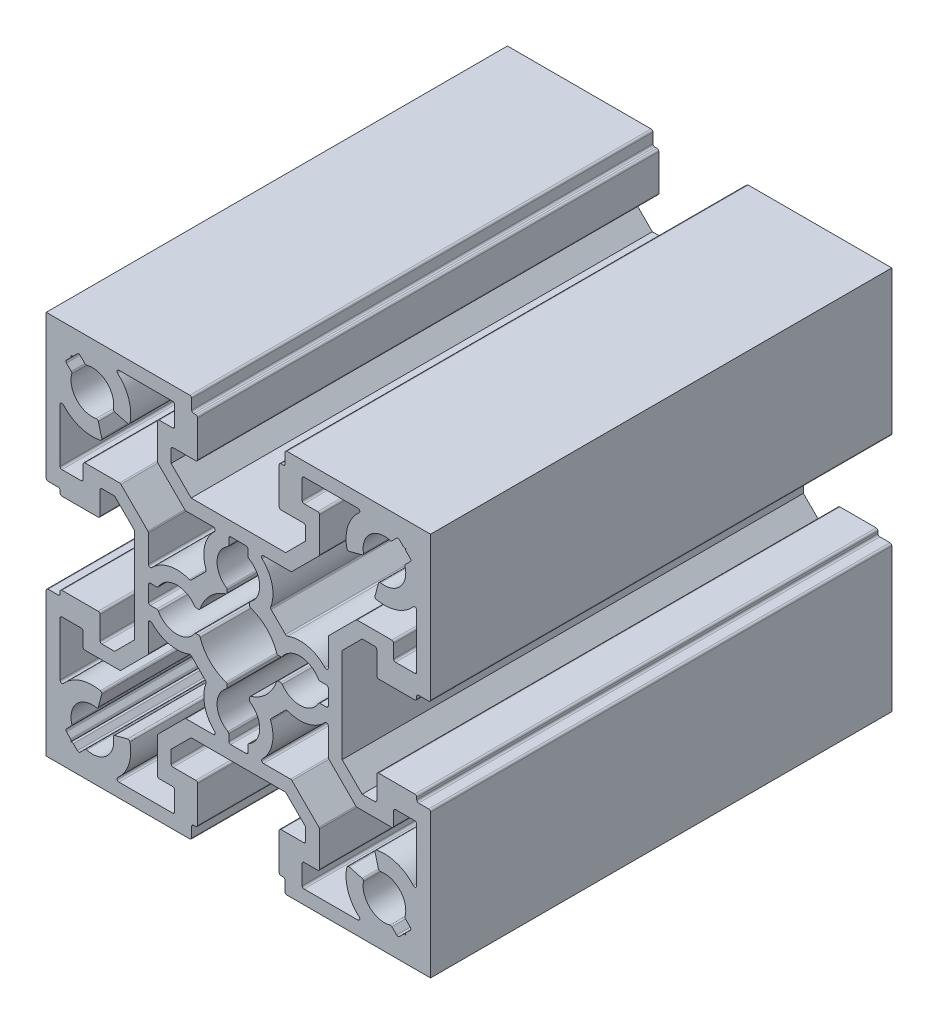
SolidWorks part; units mm, degrees
material "6061 Alaşım"
ref_plane "Ön Düzlem" through (0, 0, 0) normal (0, 0, 1) x (1, 0, 0)
ref_plane "Üst Düzlem" through (0, 0, 0) normal (0, 1, 0) x (1, 0, 0)
ref_plane "Sağ Düzlem" through (0, 0, 0) normal (1, 0, 0) x (0, 0, -1)
sketch "Çizim1" plane through (0, 0, 0) normal (0, 0, 1) x (1, 0, 0)
  line L1 (25, -25) -> (-25, -25) construction
  line L2 (25, -25) -> (25, 25) construction
  line L3 (25, 25) -> (-25, 25) construction
  line L4 (-25, -25) -> (-25, 25) construction
  line L5 (25, -25) -> (-25, 25) construction
  line L6 (25, 25) -> (-25, -25) construction
  point P0 (0, 0)
  dimension "D1" = 50
  dimension "D2" = 50
sketch "Çizim3" plane through (0, 0, 0) normal (0, 0, 1) x (1, 0, 0)
  line L0 (6.075, -24.75) -> (6.075, -23.45)
  line L1 (25, -25) -> (-25, -25) construction
  line L2 (5.825, -23.2) -> (5.55, -23.2)
  line L3 (5.3, -22.95) -> (5.3, -18.25)
  line L4 (5.55, -18) -> (8.5, -18)
  line L5 (8.75, -17.75) -> (8.75, -16.1)
  line L6 (8.75, -16.1) -> (6.15, -13.5)
  line L7 (6.15, -13.5) -> (0, -13.5)
  line L8 (0, -25) -> (0, 25) construction
  line L9 (25, 25) -> (-25, 25) construction
  line L10 (25, -25) -> (-25, 25) construction
  line L11 (6.325, -25) -> (25, -25)
  line L12 (3.265, -11.7) -> (6.792, -11.7)
  line L13 (6.9688, -11.7732) -> (10.4768, -15.2812)
  line L14 (10.55, -15.458) -> (10.55, -19.95)
  line L15 (10.3, -20.2) -> (8.55, -20.2)
  line L16 (8.3, -20.45) -> (8.3, -22.95)
  line L17 (8.55, -23.2) -> (15.5417, -23.2)
  line L18 (25, -25) -> (25, 25) construction
  line L19 (17.7059, -14.1704) -> (19, -19) construction
  line L20 (19, -19) -> (14.1704, -17.7059) construction
  line L21 (25, -25) -> (19, -19) construction
  line L22 (20.9445, -22.3588) -> (21.4749, -21.8284)
  line L23 (19.9736, -21.7414) -> (20.591, -22.3588)
  line L24 (20.7678, -22.5355) -> (22.5355, -20.7678) construction
  line L25 (22.5355, -20.7678) -> (21.6358, -19.868) construction
  line L26 (21.8284, -21.8284) -> (25, -25)
  line L27 (16.0881, -18.2198) -> (14.4182, -17.7723)
  line L28 (0, -11.7) -> (1, -11.7)
  line L29 (1.25, -11.45) -> (1.25, -10.6269)
  line L30 (0, -11.7) -> (0, -13.5)
  line L31 (6.1324, -4.2621) -> (4.2621, -6.1324)
  line L32 (5.1972, -5.1972) -> (3.6946, -3.6946)
  line L33 (1.45, -5.2044) -> (1.45, -5.4979)
  line L34 (18.2198, -16.0881) -> (17.7723, -14.4182)
  line L35 (21.7414, -19.9736) -> (22.3588, -20.591)
  line L36 (22.3588, -20.9445) -> (21.8284, -21.4749)
  line L37 (25, -6.325) -> (25, -25)
  line L38 (24.75, -6.075) -> (23.45, -6.075)
  line L39 (23.2, -5.825) -> (23.2, -5.55)
  line L40 (22.95, -5.3) -> (18.25, -5.3)
  line L41 (18, -5.55) -> (18, -8.5)
  line L42 (17.75, -8.75) -> (16.1, -8.75)
  line L43 (16.1, -8.75) -> (13.5, -6.15)
  line L44 (13.5, -6.15) -> (13.5, 0)
  line L45 (11.7, 0) -> (13.5, 0)
  line L46 (11.7, 0) -> (11.7, -1)
  line L47 (11.45, -1.25) -> (10.6269, -1.25)
  line L48 (5.2044, -1.45) -> (5.4979, -1.45)
  line L49 (11.7, -3.265) -> (11.7, -6.792)
  line L50 (11.7732, -6.9688) -> (15.2812, -10.4768)
  line L51 (15.458, -10.55) -> (19.95, -10.55)
  line L52 (20.2, -10.3) -> (20.2, -8.55)
  line L53 (20.45, -8.3) -> (22.95, -8.3)
  line L54 (23.2, -8.55) -> (23.2, -15.5417)
  line L55 (-20.9445, -22.3588) -> (-21.4749, -21.8284)
  line L56 (-19.9736, -21.7414) -> (-20.591, -22.3588)
  line L57 (-16.0881, -18.2198) -> (-14.4182, -17.7723)
  line L58 (-8.55, -23.2) -> (-15.5417, -23.2)
  line L59 (-8.3, -20.45) -> (-8.3, -22.95)
  line L60 (-10.3, -20.2) -> (-8.55, -20.2)
  line L61 (-10.55, -15.458) -> (-10.55, -19.95)
  line L62 (-6.9688, -11.7732) -> (-10.4768, -15.2812)
  line L63 (-3.265, -11.7) -> (-6.792, -11.7)
  line L64 (-4.2621, -6.1324) -> (-6.1324, -4.2621)
  line L65 (-11.7, -3.265) -> (-11.7, -6.792)
  line L66 (-11.7732, -6.9688) -> (-15.2812, -10.4768)
  line L67 (-15.458, -10.55) -> (-19.95, -10.55)
  line L68 (-20.2, -10.3) -> (-20.2, -8.55)
  line L69 (-20.45, -8.3) -> (-22.95, -8.3)
  line L70 (-23.2, -8.55) -> (-23.2, -15.5417)
  line L71 (-18.2198, -16.0881) -> (-17.7723, -14.4182)
  line L72 (-21.7414, -19.9736) -> (-22.3588, -20.591)
  line L73 (-22.3588, -20.9445) -> (-21.8284, -21.4749)
  line L74 (-25, -6.325) -> (-25, -25)
  line L75 (-24.75, -6.075) -> (-23.45, -6.075)
  line L76 (-23.2, -5.825) -> (-23.2, -5.55)
  line L77 (-22.95, -5.3) -> (-18.25, -5.3)
  line L78 (-18, -5.55) -> (-18, -8.5)
  line L79 (-17.75, -8.75) -> (-16.1, -8.75)
  line L80 (-16.1, -8.75) -> (-13.5, -6.15)
  line L81 (-13.5, -6.15) -> (-13.5, 0)
  line L82 (-11.7, 0) -> (-13.5, 0) construction
  line L83 (-11.7, 0) -> (-11.7, -1)
  line L84 (-11.45, -1.25) -> (-10.6269, -1.25)
  line L85 (-5.2044, -1.45) -> (-5.4979, -1.45)
  line L86 (-1.45, -5.2044) -> (-1.45, -5.4979)
  line L87 (-1.25, -11.45) -> (-1.25, -10.6269)
  line L88 (0, -11.7) -> (-1, -11.7)
  line L89 (0, -11.7) -> (0, -13.5)
  line L90 (-6.15, -13.5) -> (0, -13.5)
  line L91 (-8.75, -16.1) -> (-6.15, -13.5)
  line L92 (-8.75, -17.75) -> (-8.75, -16.1)
  line L93 (-5.55, -18) -> (-8.5, -18)
  line L94 (-5.3, -22.95) -> (-5.3, -18.25)
  line L95 (-5.825, -23.2) -> (-5.55, -23.2)
  line L96 (-6.075, -24.75) -> (-6.075, -23.45)
  line L97 (-6.325, -25) -> (-25, -25)
  line L98 (-22.3588, 20.9445) -> (-21.8284, 21.4749)
  line L99 (-21.7414, 19.9736) -> (-22.3588, 20.591)
  line L100 (-18.2198, 16.0881) -> (-17.7723, 14.4182)
  line L101 (-23.2, 8.55) -> (-23.2, 15.5417)
  line L102 (-20.45, 8.3) -> (-22.95, 8.3)
  line L103 (-20.2, 10.3) -> (-20.2, 8.55)
  line L104 (-15.458, 10.55) -> (-19.95, 10.55)
  line L105 (-11.7732, 6.9688) -> (-15.2812, 10.4768)
  line L106 (-11.7, 3.265) -> (-11.7, 6.792)
  line L107 (-6.1324, 4.2621) -> (-4.2621, 6.1324)
  line L108 (-3.265, 11.7) -> (-6.792, 11.7)
  line L109 (-6.9688, 11.7732) -> (-10.4768, 15.2812)
  line L110 (-10.55, 15.458) -> (-10.55, 19.95)
  line L111 (-10.3, 20.2) -> (-8.55, 20.2)
  line L112 (-8.3, 20.45) -> (-8.3, 22.95)
  line L113 (-8.55, 23.2) -> (-15.5417, 23.2)
  line L114 (-16.0881, 18.2198) -> (-14.4182, 17.7723)
  line L115 (-19.9736, 21.7414) -> (-20.591, 22.3588)
  line L116 (-20.9445, 22.3588) -> (-21.4749, 21.8284)
  line L117 (-6.325, 25) -> (-25, 25)
  line L118 (-6.075, 24.75) -> (-6.075, 23.45)
  line L119 (-5.825, 23.2) -> (-5.55, 23.2)
  line L120 (-5.3, 22.95) -> (-5.3, 18.25)
  line L121 (-5.55, 18) -> (-8.5, 18)
  line L122 (-8.75, 17.75) -> (-8.75, 16.1)
  line L123 (-8.75, 16.1) -> (-6.15, 13.5)
  line L124 (-6.15, 13.5) -> (0, 13.5)
  line L125 (0, 11.7) -> (0, 13.5)
  line L126 (0, 11.7) -> (-1, 11.7)
  line L127 (-1.25, 11.45) -> (-1.25, 10.6269)
  line L128 (-1.45, 5.2044) -> (-1.45, 5.4979)
  line L129 (-5.2044, 1.45) -> (-5.4979, 1.45)
  line L130 (-11.45, 1.25) -> (-10.6269, 1.25)
  line L131 (-11.7, 0) -> (-11.7, 1)
  line L132 (-11.7, 0) -> (-13.5, 0)
  line L133 (-13.5, 6.15) -> (-13.5, 0)
  line L134 (-16.1, 8.75) -> (-13.5, 6.15)
  line L135 (-17.75, 8.75) -> (-16.1, 8.75)
  line L136 (-18, 5.55) -> (-18, 8.5)
  line L137 (-22.95, 5.3) -> (-18.25, 5.3)
  line L138 (-23.2, 5.825) -> (-23.2, 5.55)
  line L139 (-24.75, 6.075) -> (-23.45, 6.075)
  line L140 (-25, 6.325) -> (-25, 25)
  line L141 (20.9445, 22.3588) -> (21.4749, 21.8284)
  line L142 (19.9736, 21.7414) -> (20.591, 22.3588)
  line L143 (16.0881, 18.2198) -> (14.4182, 17.7723)
  line L144 (8.55, 23.2) -> (15.5417, 23.2)
  line L145 (8.3, 20.45) -> (8.3, 22.95)
  line L146 (10.3, 20.2) -> (8.55, 20.2)
  line L147 (10.55, 15.458) -> (10.55, 19.95)
  line L148 (6.9688, 11.7732) -> (10.4768, 15.2812)
  line L149 (3.265, 11.7) -> (6.792, 11.7)
  line L150 (4.2621, 6.1324) -> (6.1324, 4.2621)
  line L151 (11.7, 3.265) -> (11.7, 6.792)
  line L152 (11.7732, 6.9688) -> (15.2812, 10.4768)
  line L153 (15.458, 10.55) -> (19.95, 10.55)
  line L154 (20.2, 10.3) -> (20.2, 8.55)
  line L155 (20.45, 8.3) -> (22.95, 8.3)
  line L156 (23.2, 8.55) -> (23.2, 15.5417)
  line L157 (18.2198, 16.0881) -> (17.7723, 14.4182)
  line L158 (21.7414, 19.9736) -> (22.3588, 20.591)
  line L159 (22.3588, 20.9445) -> (21.8284, 21.4749)
  line L160 (25, 6.325) -> (25, 25)
  line L161 (24.75, 6.075) -> (23.45, 6.075)
  line L162 (23.2, 5.825) -> (23.2, 5.55)
  line L163 (22.95, 5.3) -> (18.25, 5.3)
  line L164 (18, 5.55) -> (18, 8.5)
  line L165 (17.75, 8.75) -> (16.1, 8.75)
  line L166 (16.1, 8.75) -> (13.5, 6.15)
  line L167 (13.5, 6.15) -> (13.5, 0)
  line L168 (11.7, 0) -> (13.5, 0)
  line L169 (11.7, 0) -> (11.7, 1)
  line L170 (11.45, 1.25) -> (10.6269, 1.25)
  line L171 (5.2044, 1.45) -> (5.4979, 1.45)
  line L172 (1.45, 5.2044) -> (1.45, 5.4979)
  line L173 (1.25, 11.45) -> (1.25, 10.6269)
  line L174 (0, 11.7) -> (1, 11.7)
  line L175 (0, 11.7) -> (0, 13.5)
  line L176 (6.15, 13.5) -> (0, 13.5)
  line L177 (8.75, 16.1) -> (6.15, 13.5)
  line L178 (8.75, 17.75) -> (8.75, 16.1)
  line L179 (5.55, 18) -> (8.5, 18)
  line L180 (5.3, 22.95) -> (5.3, 18.25)
  line L181 (5.825, 23.2) -> (5.55, 23.2)
  line L182 (6.075, 24.75) -> (6.075, 23.45)
  line L183 (6.325, 25) -> (25, 25)
  circle A0 centre (19, -19) radius 2.775 construction
  circle A1 centre (0, -8) radius 2.775 construction
  circle A2 centre (19, -19) radius 5 construction
  arc A3 (14.109, -17.9619) -> (15.7064, -22.7619) centre (19, -19) ccw
  arc A4 (16.2694, -18.5058) -> (19.731, -21.677) centre (19, -19) ccw
  circle A5 centre (0, -8) radius 4.5 construction
  arc A6 (3.0931, -11.2684) -> (4.2052, -6.3981) centre (0, -8) ccw
  circle A7 centre (0, 0) radius 5.225 construction
  arc A8 (4.9667, -1.6224) -> (1.6224, -4.9667) centre (0, 0) cw
  arc A9 (1.5595, -5.7047) -> (1.376, -10.4098) centre (0, -8) cw
  arc A10 (14.4182, -17.7723) -> (14.109, -17.9619) centre (14.3535, -18.0138) ccw
  arc A11 (16.2694, -18.5058) -> (16.0881, -18.2198) centre (16.0234, -18.4612) ccw
  arc A12 (21.4749, -21.8284) -> (21.8284, -21.8284) centre (21.6517, -22.0052) cw
  arc A13 (19.9736, -21.7414) -> (19.731, -21.677) centre (19.7968, -21.9182) ccw
  arc A14 (20.591, -22.3588) -> (20.9445, -22.3588) centre (20.7678, -22.182) ccw
  arc A15 (4.2052, -6.3981) -> (4.2621, -6.1324) centre (4.4389, -6.3092) cw
  arc A16 (1.6224, -4.9667) -> (1.45, -5.2044) centre (1.7, -5.2044) ccw
  arc A17 (1.45, -5.4979) -> (1.5595, -5.7047) centre (1.7, -5.4979) ccw
  arc A18 (1.25, -10.6269) -> (1.376, -10.4098) centre (1.5, -10.6269) cw
  arc A19 (1, -11.7) -> (1.25, -11.45) centre (1, -11.45) ccw
  arc A20 (3.265, -11.7) -> (3.0931, -11.2684) centre (3.265, -11.45) cw
  arc A21 (6.792, -11.7) -> (6.9688, -11.7732) centre (6.792, -11.95) cw
  arc A22 (10.4768, -15.2812) -> (10.55, -15.458) centre (10.3, -15.458) cw
  arc A23 (15.5417, -23.2) -> (15.7064, -22.7619) centre (15.5417, -22.95) ccw
  arc A24 (8.3, -22.95) -> (8.55, -23.2) centre (8.55, -22.95) ccw
  arc A25 (8.55, -20.2) -> (8.3, -20.45) centre (8.55, -20.45) ccw
  arc A26 (10.55, -19.95) -> (10.3, -20.2) centre (10.3, -19.95) cw
  arc A27 (6.075, -24.75) -> (6.325, -25) centre (6.325, -24.75) ccw
  arc A28 (6.075, -23.45) -> (5.825, -23.2) centre (5.825, -23.45) ccw
  arc A29 (5.55, -23.2) -> (5.3, -22.95) centre (5.55, -22.95) cw
  arc A30 (5.3, -18.25) -> (5.55, -18) centre (5.55, -18.25) cw
  arc A31 (8.5, -18) -> (8.75, -17.75) centre (8.5, -17.75) ccw
  arc A32 (18.5058, -16.2694) -> (18.2198, -16.0881) centre (18.4612, -16.0234) cw
  arc A33 (18.5058, -16.2694) -> (21.677, -19.731) centre (19, -19) cw
  arc A34 (21.7414, -19.9736) -> (21.677, -19.731) centre (21.9182, -19.7968) cw
  arc A35 (22.3588, -20.591) -> (22.3588, -20.9445) centre (22.182, -20.7678) cw
  arc A36 (21.8284, -21.4749) -> (21.8284, -21.8284) centre (22.0052, -21.6517) ccw
  arc A37 (24.75, -6.075) -> (25, -6.325) centre (24.75, -6.325) cw
  arc A38 (23.45, -6.075) -> (23.2, -5.825) centre (23.45, -5.825) cw
  arc A39 (23.2, -5.55) -> (22.95, -5.3) centre (22.95, -5.55) ccw
  arc A40 (18.25, -5.3) -> (18, -5.55) centre (18.25, -5.55) ccw
  arc A41 (18, -8.5) -> (17.75, -8.75) centre (17.75, -8.5) cw
  arc A42 (11.7, -1) -> (11.45, -1.25) centre (11.45, -1) cw
  arc A43 (10.6269, -1.25) -> (10.4098, -1.376) centre (10.6269, -1.5) ccw
  arc A44 (5.7047, -1.5595) -> (10.4098, -1.376) centre (8, 0) ccw
  arc A45 (5.4979, -1.45) -> (5.7047, -1.5595) centre (5.4979, -1.7) cw
  arc A46 (4.9667, -1.6224) -> (5.2044, -1.45) centre (5.2044, -1.7) cw
  arc A47 (6.3981, -4.2052) -> (6.1324, -4.2621) centre (6.3092, -4.4389) ccw
  arc A48 (11.2684, -3.0931) -> (6.3981, -4.2052) centre (8, 0) cw
  arc A49 (11.7, -3.265) -> (11.2684, -3.0931) centre (11.45, -3.265) ccw
  arc A50 (11.7, -6.792) -> (11.7732, -6.9688) centre (11.95, -6.792) ccw
  arc A51 (15.2812, -10.4768) -> (15.458, -10.55) centre (15.458, -10.3) ccw
  arc A52 (19.95, -10.55) -> (20.2, -10.3) centre (19.95, -10.3) ccw
  arc A53 (20.2, -8.55) -> (20.45, -8.3) centre (20.45, -8.55) cw
  arc A54 (22.95, -8.3) -> (23.2, -8.55) centre (22.95, -8.55) cw
  arc A55 (23.2, -15.5417) -> (22.7619, -15.7064) centre (22.95, -15.5417) cw
  arc A56 (17.9619, -14.109) -> (22.7619, -15.7064) centre (19, -19) cw
  arc A57 (17.7723, -14.4182) -> (17.9619, -14.109) centre (18.0138, -14.3535) cw
  arc A58 (-21.4749, -21.8284) -> (-21.8284, -21.8284) centre (-21.6517, -22.0052) ccw
  arc A59 (-20.591, -22.3588) -> (-20.9445, -22.3588) centre (-20.7678, -22.182) cw
  arc A60 (-19.9736, -21.7414) -> (-19.731, -21.677) centre (-19.7968, -21.9182) cw
  arc A61 (-16.2694, -18.5058) -> (-19.731, -21.677) centre (-19, -19) cw
  arc A62 (-16.2694, -18.5058) -> (-16.0881, -18.2198) centre (-16.0234, -18.4612) cw
  arc A63 (-14.4182, -17.7723) -> (-14.109, -17.9619) centre (-14.3535, -18.0138) cw
  arc A64 (-14.109, -17.9619) -> (-15.7064, -22.7619) centre (-19, -19) cw
  arc A65 (-15.5417, -23.2) -> (-15.7064, -22.7619) centre (-15.5417, -22.95) cw
  arc A66 (-8.3, -22.95) -> (-8.55, -23.2) centre (-8.55, -22.95) cw
  arc A67 (-8.55, -20.2) -> (-8.3, -20.45) centre (-8.55, -20.45) cw
  arc A68 (-10.55, -19.95) -> (-10.3, -20.2) centre (-10.3, -19.95) ccw
  arc A69 (-10.4768, -15.2812) -> (-10.55, -15.458) centre (-10.3, -15.458) ccw
  arc A70 (-6.792, -11.7) -> (-6.9688, -11.7732) centre (-6.792, -11.95) ccw
  arc A71 (-3.265, -11.7) -> (-3.0931, -11.2684) centre (-3.265, -11.45) ccw
  arc A72 (-3.0931, -11.2684) -> (-4.2052, -6.3981) centre (0, -8) cw
  arc A73 (-4.2052, -6.3981) -> (-4.2621, -6.1324) centre (-4.4389, -6.3092) ccw
  arc A74 (-6.3981, -4.2052) -> (-6.1324, -4.2621) centre (-6.3092, -4.4389) cw
  arc A75 (-11.2684, -3.0931) -> (-6.3981, -4.2052) centre (-8, 0) ccw
  arc A76 (-11.7, -3.265) -> (-11.2684, -3.0931) centre (-11.45, -3.265) cw
  arc A77 (-11.7, -6.792) -> (-11.7732, -6.9688) centre (-11.95, -6.792) cw
  arc A78 (-15.2812, -10.4768) -> (-15.458, -10.55) centre (-15.458, -10.3) cw
  arc A79 (-19.95, -10.55) -> (-20.2, -10.3) centre (-19.95, -10.3) cw
  arc A80 (-20.2, -8.55) -> (-20.45, -8.3) centre (-20.45, -8.55) ccw
  arc A81 (-22.95, -8.3) -> (-23.2, -8.55) centre (-22.95, -8.55) ccw
  arc A82 (-23.2, -15.5417) -> (-22.7619, -15.7064) centre (-22.95, -15.5417) ccw
  arc A83 (-17.9619, -14.109) -> (-22.7619, -15.7064) centre (-19, -19) ccw
  arc A84 (-17.7723, -14.4182) -> (-17.9619, -14.109) centre (-18.0138, -14.3535) ccw
  arc A85 (-18.5058, -16.2694) -> (-18.2198, -16.0881) centre (-18.4612, -16.0234) ccw
  arc A86 (-18.5058, -16.2694) -> (-21.677, -19.731) centre (-19, -19) ccw
  arc A87 (-21.7414, -19.9736) -> (-21.677, -19.731) centre (-21.9182, -19.7968) ccw
  arc A88 (-22.3588, -20.591) -> (-22.3588, -20.9445) centre (-22.182, -20.7678) ccw
  arc A89 (-21.8284, -21.4749) -> (-21.8284, -21.8284) centre (-22.0052, -21.6517) cw
  arc A90 (-24.75, -6.075) -> (-25, -6.325) centre (-24.75, -6.325) ccw
  arc A91 (-23.45, -6.075) -> (-23.2, -5.825) centre (-23.45, -5.825) ccw
  arc A92 (-23.2, -5.55) -> (-22.95, -5.3) centre (-22.95, -5.55) cw
  arc A93 (-18.25, -5.3) -> (-18, -5.55) centre (-18.25, -5.55) cw
  arc A94 (-18, -8.5) -> (-17.75, -8.75) centre (-17.75, -8.5) ccw
  arc A95 (-11.7, -1) -> (-11.45, -1.25) centre (-11.45, -1) ccw
  arc A96 (-10.6269, -1.25) -> (-10.4098, -1.376) centre (-10.6269, -1.5) cw
  arc A97 (-5.7047, -1.5595) -> (-10.4098, -1.376) centre (-8, 0) cw
  arc A98 (-5.4979, -1.45) -> (-5.7047, -1.5595) centre (-5.4979, -1.7) ccw
  arc A99 (-4.9667, -1.6224) -> (-5.2044, -1.45) centre (-5.2044, -1.7) ccw
  arc A100 (-1.6224, -4.9667) -> (-4.9667, -1.6224) centre (0, 0) cw
  arc A101 (-1.6224, -4.9667) -> (-1.45, -5.2044) centre (-1.7, -5.2044) cw
  arc A102 (-1.45, -5.4979) -> (-1.5595, -5.7047) centre (-1.7, -5.4979) cw
  arc A103 (-1.5595, -5.7047) -> (-1.376, -10.4098) centre (0, -8) ccw
  arc A104 (-1.25, -10.6269) -> (-1.376, -10.4098) centre (-1.5, -10.6269) ccw
  arc A105 (-1, -11.7) -> (-1.25, -11.45) centre (-1, -11.45) cw
  arc A106 (-8.5, -18) -> (-8.75, -17.75) centre (-8.5, -17.75) cw
  arc A107 (-5.3, -18.25) -> (-5.55, -18) centre (-5.55, -18.25) ccw
  arc A108 (-5.55, -23.2) -> (-5.3, -22.95) centre (-5.55, -22.95) ccw
  arc A109 (-6.075, -23.45) -> (-5.825, -23.2) centre (-5.825, -23.45) cw
  arc A110 (-6.075, -24.75) -> (-6.325, -25) centre (-6.325, -24.75) cw
  arc A111 (-21.8284, 21.4749) -> (-21.8284, 21.8284) centre (-22.0052, 21.6517) ccw
  arc A112 (-22.3588, 20.591) -> (-22.3588, 20.9445) centre (-22.182, 20.7678) cw
  arc A113 (-21.7414, 19.9736) -> (-21.677, 19.731) centre (-21.9182, 19.7968) cw
  arc A114 (-18.5058, 16.2694) -> (-21.677, 19.731) centre (-19, 19) cw
  arc A115 (-18.5058, 16.2694) -> (-18.2198, 16.0881) centre (-18.4612, 16.0234) cw
  arc A116 (-17.7723, 14.4182) -> (-17.9619, 14.109) centre (-18.0138, 14.3535) cw
  arc A117 (-17.9619, 14.109) -> (-22.7619, 15.7064) centre (-19, 19) cw
  arc A118 (-23.2, 15.5417) -> (-22.7619, 15.7064) centre (-22.95, 15.5417) cw
  arc A119 (-22.95, 8.3) -> (-23.2, 8.55) centre (-22.95, 8.55) cw
  arc A120 (-20.2, 8.55) -> (-20.45, 8.3) centre (-20.45, 8.55) cw
  arc A121 (-19.95, 10.55) -> (-20.2, 10.3) centre (-19.95, 10.3) ccw
  arc A122 (-15.2812, 10.4768) -> (-15.458, 10.55) centre (-15.458, 10.3) ccw
  arc A123 (-11.7, 6.792) -> (-11.7732, 6.9688) centre (-11.95, 6.792) ccw
  arc A124 (-11.7, 3.265) -> (-11.2684, 3.0931) centre (-11.45, 3.265) ccw
  arc A125 (-11.2684, 3.0931) -> (-6.3981, 4.2052) centre (-8, 0) cw
  arc A126 (-6.3981, 4.2052) -> (-6.1324, 4.2621) centre (-6.3092, 4.4389) ccw
  arc A127 (-4.2052, 6.3981) -> (-4.2621, 6.1324) centre (-4.4389, 6.3092) cw
  arc A128 (-3.0931, 11.2684) -> (-4.2052, 6.3981) centre (0, 8) ccw
  arc A129 (-3.265, 11.7) -> (-3.0931, 11.2684) centre (-3.265, 11.45) cw
  arc A130 (-6.792, 11.7) -> (-6.9688, 11.7732) centre (-6.792, 11.95) cw
  arc A131 (-10.4768, 15.2812) -> (-10.55, 15.458) centre (-10.3, 15.458) cw
  arc A132 (-10.55, 19.95) -> (-10.3, 20.2) centre (-10.3, 19.95) cw
  arc A133 (-8.55, 20.2) -> (-8.3, 20.45) centre (-8.55, 20.45) ccw
  arc A134 (-8.3, 22.95) -> (-8.55, 23.2) centre (-8.55, 22.95) ccw
  arc A135 (-15.5417, 23.2) -> (-15.7064, 22.7619) centre (-15.5417, 22.95) ccw
  arc A136 (-14.109, 17.9619) -> (-15.7064, 22.7619) centre (-19, 19) ccw
  arc A137 (-14.4182, 17.7723) -> (-14.109, 17.9619) centre (-14.3535, 18.0138) ccw
  arc A138 (-16.2694, 18.5058) -> (-16.0881, 18.2198) centre (-16.0234, 18.4612) ccw
  arc A139 (-16.2694, 18.5058) -> (-19.731, 21.677) centre (-19, 19) ccw
  arc A140 (-19.9736, 21.7414) -> (-19.731, 21.677) centre (-19.7968, 21.9182) ccw
  arc A141 (-20.591, 22.3588) -> (-20.9445, 22.3588) centre (-20.7678, 22.182) ccw
  arc A142 (-21.4749, 21.8284) -> (-21.8284, 21.8284) centre (-21.6517, 22.0052) cw
  arc A143 (-6.075, 24.75) -> (-6.325, 25) centre (-6.325, 24.75) ccw
  arc A144 (-6.075, 23.45) -> (-5.825, 23.2) centre (-5.825, 23.45) ccw
  arc A145 (-5.55, 23.2) -> (-5.3, 22.95) centre (-5.55, 22.95) cw
  arc A146 (-5.3, 18.25) -> (-5.55, 18) centre (-5.55, 18.25) cw
  arc A147 (-8.5, 18) -> (-8.75, 17.75) centre (-8.5, 17.75) ccw
  arc A148 (-1, 11.7) -> (-1.25, 11.45) centre (-1, 11.45) ccw
  arc A149 (-1.25, 10.6269) -> (-1.376, 10.4098) centre (-1.5, 10.6269) cw
  arc A150 (-1.5595, 5.7047) -> (-1.376, 10.4098) centre (0, 8) cw
  arc A151 (-1.45, 5.4979) -> (-1.5595, 5.7047) centre (-1.7, 5.4979) ccw
  arc A152 (-1.6224, 4.9667) -> (-1.45, 5.2044) centre (-1.7, 5.2044) ccw
  arc A153 (-4.9667, 1.6224) -> (-1.6224, 4.9667) centre (0, 0) cw
  arc A154 (-4.9667, 1.6224) -> (-5.2044, 1.45) centre (-5.2044, 1.7) cw
  arc A155 (-5.4979, 1.45) -> (-5.7047, 1.5595) centre (-5.4979, 1.7) cw
  arc A156 (-5.7047, 1.5595) -> (-10.4098, 1.376) centre (-8, 0) ccw
  arc A157 (-10.6269, 1.25) -> (-10.4098, 1.376) centre (-10.6269, 1.5) ccw
  arc A158 (-11.7, 1) -> (-11.45, 1.25) centre (-11.45, 1) cw
  arc A159 (-18, 8.5) -> (-17.75, 8.75) centre (-17.75, 8.5) cw
  arc A160 (-18.25, 5.3) -> (-18, 5.55) centre (-18.25, 5.55) ccw
  arc A161 (-23.2, 5.55) -> (-22.95, 5.3) centre (-22.95, 5.55) ccw
  arc A162 (-23.45, 6.075) -> (-23.2, 5.825) centre (-23.45, 5.825) cw
  arc A163 (-24.75, 6.075) -> (-25, 6.325) centre (-24.75, 6.325) cw
  arc A164 (21.4749, 21.8284) -> (21.8284, 21.8284) centre (21.6517, 22.0052) ccw
  arc A165 (20.591, 22.3588) -> (20.9445, 22.3588) centre (20.7678, 22.182) cw
  arc A166 (19.9736, 21.7414) -> (19.731, 21.677) centre (19.7968, 21.9182) cw
  arc A167 (16.2694, 18.5058) -> (19.731, 21.677) centre (19, 19) cw
  arc A168 (16.2694, 18.5058) -> (16.0881, 18.2198) centre (16.0234, 18.4612) cw
  arc A169 (14.4182, 17.7723) -> (14.109, 17.9619) centre (14.3535, 18.0138) cw
  arc A170 (14.109, 17.9619) -> (15.7064, 22.7619) centre (19, 19) cw
  arc A171 (15.5417, 23.2) -> (15.7064, 22.7619) centre (15.5417, 22.95) cw
  arc A172 (8.3, 22.95) -> (8.55, 23.2) centre (8.55, 22.95) cw
  arc A173 (8.55, 20.2) -> (8.3, 20.45) centre (8.55, 20.45) cw
  arc A174 (10.55, 19.95) -> (10.3, 20.2) centre (10.3, 19.95) ccw
  arc A175 (10.4768, 15.2812) -> (10.55, 15.458) centre (10.3, 15.458) ccw
  arc A176 (6.792, 11.7) -> (6.9688, 11.7732) centre (6.792, 11.95) ccw
  arc A177 (3.265, 11.7) -> (3.0931, 11.2684) centre (3.265, 11.45) ccw
  arc A178 (3.0931, 11.2684) -> (4.2052, 6.3981) centre (0, 8) cw
  arc A179 (4.2052, 6.3981) -> (4.2621, 6.1324) centre (4.4389, 6.3092) ccw
  arc A180 (6.3981, 4.2052) -> (6.1324, 4.2621) centre (6.3092, 4.4389) cw
  arc A181 (11.2684, 3.0931) -> (6.3981, 4.2052) centre (8, 0) ccw
  arc A182 (11.7, 3.265) -> (11.2684, 3.0931) centre (11.45, 3.265) cw
  arc A183 (11.7, 6.792) -> (11.7732, 6.9688) centre (11.95, 6.792) cw
  arc A184 (15.2812, 10.4768) -> (15.458, 10.55) centre (15.458, 10.3) cw
  arc A185 (19.95, 10.55) -> (20.2, 10.3) centre (19.95, 10.3) cw
  arc A186 (20.2, 8.55) -> (20.45, 8.3) centre (20.45, 8.55) ccw
  arc A187 (22.95, 8.3) -> (23.2, 8.55) centre (22.95, 8.55) ccw
  arc A188 (23.2, 15.5417) -> (22.7619, 15.7064) centre (22.95, 15.5417) ccw
  arc A189 (17.9619, 14.109) -> (22.7619, 15.7064) centre (19, 19) ccw
  arc A190 (17.7723, 14.4182) -> (17.9619, 14.109) centre (18.0138, 14.3535) ccw
  arc A191 (18.5058, 16.2694) -> (18.2198, 16.0881) centre (18.4612, 16.0234) ccw
  arc A192 (18.5058, 16.2694) -> (21.677, 19.731) centre (19, 19) ccw
  arc A193 (21.7414, 19.9736) -> (21.677, 19.731) centre (21.9182, 19.7968) ccw
  arc A194 (22.3588, 20.591) -> (22.3588, 20.9445) centre (22.182, 20.7678) ccw
  arc A195 (21.8284, 21.4749) -> (21.8284, 21.8284) centre (22.0052, 21.6517) cw
  arc A196 (24.75, 6.075) -> (25, 6.325) centre (24.75, 6.325) ccw
  arc A197 (23.45, 6.075) -> (23.2, 5.825) centre (23.45, 5.825) ccw
  arc A198 (23.2, 5.55) -> (22.95, 5.3) centre (22.95, 5.55) cw
  arc A199 (18.25, 5.3) -> (18, 5.55) centre (18.25, 5.55) cw
  arc A200 (18, 8.5) -> (17.75, 8.75) centre (17.75, 8.5) ccw
  arc A201 (11.7, 1) -> (11.45, 1.25) centre (11.45, 1) ccw
  arc A202 (10.6269, 1.25) -> (10.4098, 1.376) centre (10.6269, 1.5) cw
  arc A203 (5.7047, 1.5595) -> (10.4098, 1.376) centre (8, 0) cw
  arc A204 (5.4979, 1.45) -> (5.7047, 1.5595) centre (5.4979, 1.7) ccw
  arc A205 (4.9667, 1.6224) -> (5.2044, 1.45) centre (5.2044, 1.7) ccw
  arc A206 (1.6224, 4.9667) -> (4.9667, 1.6224) centre (0, 0) cw
  arc A207 (1.6224, 4.9667) -> (1.45, 5.2044) centre (1.7, 5.2044) cw
  arc A208 (1.45, 5.4979) -> (1.5595, 5.7047) centre (1.7, 5.4979) cw
  arc A209 (1.5595, 5.7047) -> (1.376, 10.4098) centre (0, 8) ccw
  arc A210 (1.25, 10.6269) -> (1.376, 10.4098) centre (1.5, 10.6269) ccw
  arc A211 (1, 11.7) -> (1.25, 11.45) centre (1, 11.45) cw
  arc A212 (8.5, 18) -> (8.75, 17.75) centre (8.5, 17.75) cw
  arc A213 (5.3, 18.25) -> (5.55, 18) centre (5.55, 18.25) ccw
  arc A214 (5.55, 23.2) -> (5.3, 22.95) centre (5.55, 22.95) ccw
  arc A215 (6.075, 23.45) -> (5.825, 23.2) centre (5.825, 23.45) cw
  arc A216 (6.075, 24.75) -> (6.325, 25) centre (6.325, 24.75) cw
  point P45 (21.6517, -21.6517)
  point P63 (16.3196, -18.2818)
  point P66 (21.6517, -21.6517)
  point P69 (19.868, -21.6358)
  point P75 (4.1454, -6.2491)
  point P78 (1.45, -5.0198)
  point P81 (1.45, -5.634)
  point P84 (1.25, -10.4775)
  point P89 (2.5612, -11.7)
  point P96 (16.2871, -23.2)
  point P105 (6.075, -25)
  point P108 (6.075, -23.2)
  point P622 (0, 0)
  dimension "D9" = 5.55
  dimension "D10" = 5.55
  dimension "D11" = 10
  dimension "D20" = 30
  dimension "D25" = 9
  dimension "D28" = 0.25
  dimension "D1" = 10.6
  dimension "D2" = 7
  dimension "D3" = 11.5
  dimension "D4" = 12.15
  dimension "D5" = 38
  dimension "D6" = 17.5
  dimension "D7" = 135
  dimension "D8" = 1.8
  dimension "D12" = 1.8
  dimension "D13" = 1.8
  dimension "D14" = 6.15
  dimension "D15" = 1.8
  dimension "D16" = 1.8
  dimension "D17" = 3
  dimension "D18" = 3
  dimension "D19" = 8
  dimension "D21" = 30
  dimension "D22" = 2.5
  dimension "D23" = 3.75
  dimension "D24" = 2.5
  dimension "D26" = 7.35
  dimension "D27" = 1.45
  dimension "D29" = 4
extrude "Yükseklik-Ekstrüzyon1" add sketch "Çizim3" along normal blind 60 contours A163 L139 A162 L138 A161 L137 A160 L136 A159 L135 L134 L133 L132 L131 A158 L130 A157 A156 A155 L129 A154 A153 A152 L128 A151 A150 A149 L127 A148 L126 L125 L124 L123 L122 A147 L121 A146 L120 A145 L119 A144 L118 A143 L117 L140 A142 L116 A141 L115 A140 | A110 L96 A109 L95 A108 L94 A107 L93 A106 L92 L91 L90 L30 L88 A105 L87 A104 A103 A102 L86 A101 A100 A99 L85 A98 A97 A96 L84 A95 L83 L132 L81 L80 L79 A94 L78 A93 L77 A92 L76 A91 L75 A90 L74 L97 A89 L73 A88 L72 A87 | A31 L4 A30 L3 A29 L2 A28 L0 A27 L11 L26 A12 L22 A14 L23 A13 A4 A11 L27 A10 A3 A23 L17 A24 L16 A25 L15 A26 L14 A22 L13 A21 L12 A20 A6 A15 L31 L32 A8 A16 L33 A17 A9 A18 L29 A19 L28 L30 L7 L6 L5 | A57 L34 A32 A33 A34 L35 A35 L36 A36 L26 L37 A37 L38 A38 L39 A39 L40 A40 L41 A41 L42 L43 L44 L45 L46 A42 L47 A43 A44 A45 L48 A46 A8 L32 L31 A47 A48 A49 L49 A50 L50 A51 L51 A52 L52 A53 L53 A54 L54 A55 A56 | A216 L182 A215 L181 A214 L180 A213 L179 A212 L178 L177 L176 L125 L174 A211 L173 A210 A209 A208 L172 A207 A206 A205 L171 A204 A203 A202 L170 A201 L169 L45 L167 L166 L165 A200 L164 A199 L163 A198 L162 A197 L161 A196 L160 L183 A195 L159 A194 L158 A193 region at (10.3721, -18.3481, 0) region at (18.3481, -10.3721, 0) region at (-3.075, -13.1464, 0) region at (12.6, 0.3536, 0) region at (-12.6, 0.3536, 0)
